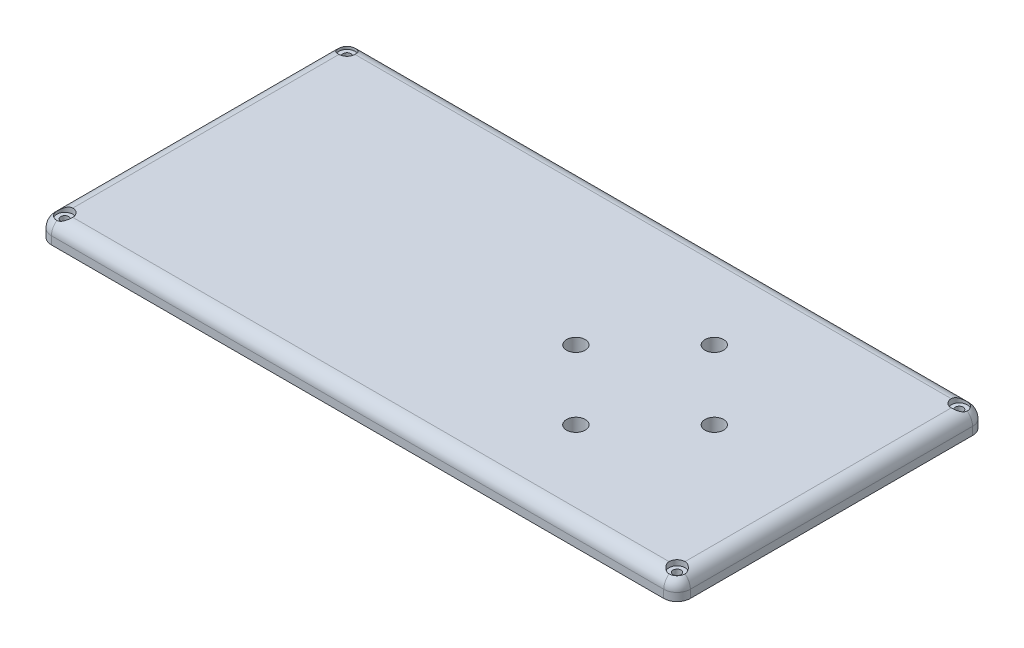
SolidWorks part; units mm, degrees
ref_plane "Front Plane" through (0, 0, 0) normal (0, 0, 1) x (1, 0, 0)
ref_plane "Top Plane" through (0, 0, 0) normal (0, 1, 0) x (1, 0, 0)
ref_plane "Right Plane" through (0, 0, 0) normal (1, 0, 0) x (0, 0, -1)
sketch "Sketch1" plane through (0, 0, 0) normal (0, 1, 0) x (1, 0, 0)
  line L1 (-120, 58) -> (120, 58)
  line L2 (-120, 58) -> (-120, -58)
  line L3 (-120, -58) -> (120, -58)
  line L4 (120, 58) -> (120, -58)
  line L5 (-120, 58) -> (120, -58) construction
  line L6 (-120, -58) -> (120, 58) construction
  point P0 (0, 0)
  dimension "D1" = 240
  dimension "D2" = 116
extrude "Boss-Extrude1" add sketch "Sketch1" along normal blind 8
fillet "Fillet1" radius 5 4 edges at (-120, 4, 58) (-120, 4, -58) (120, 4, -58) (120, 4, 58)
sketch "Sketch2" plane through (0, 8, 0) normal (0, 1, 0) x (1, 0, 0)
  circle A0 centre (-115, -53) radius 1.5
  circle A1 centre (-115, 53) radius 1.5
  circle A2 centre (115, 53) radius 1.5
  circle A3 centre (115, -53) radius 1.5
  dimension "D1" = 3
  dimension "D2" = 3
  dimension "D3" = 3
  dimension "D4" = 3
extrude "Cut-Extrude1" cut sketch "Sketch2" against normal up to next
fillet "Fillet2" radius 5 4 edges at (0, 8, -58) (120, 8, 0) (0, 8, 58) (-120, 8, 0)
sketch "Sketch3" plane through (0, 8, 0) normal (0, 1, 0) x (1, 0, 0)
  line L0 (0, 58) -> (0, -58) construction
  line L1 (-115, 58) -> (115, 58) construction
  line L2 (115, -58) -> (-115, -58) construction
  line L3 (-120, 0) -> (115, 0) construction
  line L4 (-120, -53) -> (-120, 53) construction
  line L5 (115, -51.5) -> (115, 51.5) construction
  circle A0 centre (-115, 53) radius 3
  circle A1 centre (-115, 53) radius 1.5
  circle A2 centre (-115, -53) radius 1.5
  circle A3 centre (-115, -53) radius 3
  circle A4 centre (115, -53) radius 3
  circle A5 centre (115, -53) radius 1.5
  circle A6 centre (115, 53) radius 1.5
  circle A7 centre (115, 53) radius 3
  dimension "D1" = 3
  dimension "D2" = 6
extrude "Cut-Extrude2" cut sketch "Sketch3" against normal blind 2
shell "Shell1" thickness 5 removed face at (115, 0, 54.5)
sketch "Sketch4" plane through (0, 8, 0) normal (0, 1, 0) x (1, 0, 0)
  circle A0 centre (50, 0) radius 26 construction
  circle A1 centre (50, 0) radius 32.5 construction
  circle A2 centre (24, 0) radius 3.5
  circle A3 centre (50, 26) radius 3.5
  circle A4 centre (76, 0) radius 3.5
  circle A5 centre (50, -26) radius 3.5
  dimension "D1" = 52
  dimension "D2" = 65
  dimension "D4" = 7
  dimension "D5" = 7
  dimension "D6" = 7
  dimension "D7" = 7
  dimension "D3" = 50
extrude "Cut-Extrude3" cut sketch "Sketch4" against normal up to next
